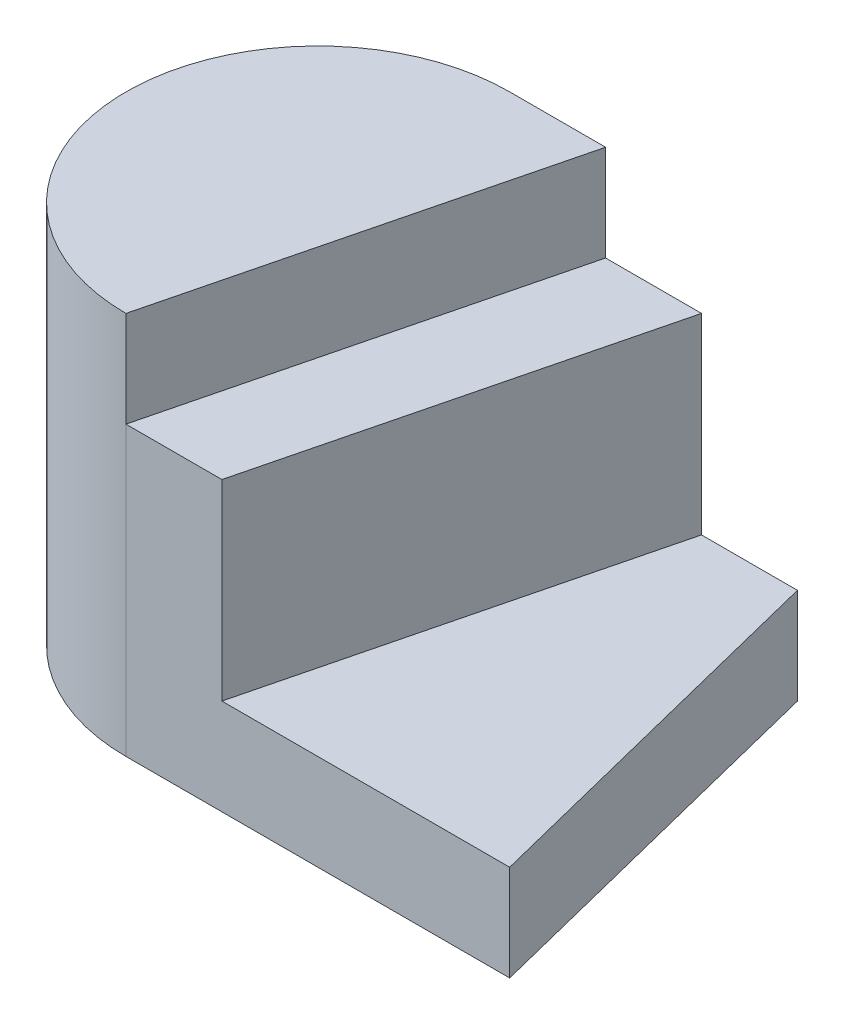
SolidWorks part; units mm, degrees
ref_plane "前基準面" through (0, 0, 0) normal (0, 0, 1) x (1, 0, 0)
ref_plane "上基準面" through (0, 0, 0) normal (0, 1, 0) x (1, 0, 0)
ref_plane "右基準面" through (0, 0, 0) normal (1, 0, 0) x (0, 0, -1)
sketch "草圖1" plane through (0, 0, 0) normal (0, 1, 0) x (1, 0, 0)
  line L0 (0, 0) -> (27.1901, 0) construction
  line L1 (0, 2) -> (3, 2)
  line L2 (3, 2) -> (4, -2)
  line L3 (4, -2) -> (0, -2)
  line L4 (0, -2) -> (1, 2)
  line L5 (1, 2) -> (2, 2)
  line L6 (2, 2) -> (1, -2)
  arc A0 (0, 2) -> (0, -2) centre (0, 0) ccw
  dimension "D1" = 4
  dimension "D2" = 3
  dimension "D3" = 4
  dimension "D4" = 1
  dimension "D5" = 1
extrude "填料-伸長2" add sketch "草圖1" along normal blind 4 contours L1 A0 L4 region at (-0.5634, 0, -0.161)
extrude "填料-伸長3" add sketch "草圖1<4>" along normal blind 3 contours L0 L4 L3 L6 | L4 L0 L6 L1 region at (1.25, 0, -1) region at (0.75, 0, 1)
sketch "草圖1<4>" plane through (0, 0, 0) normal (0, 1, 0) x (1, 0, 0) same geometry as "草圖1"
extrude "填料-伸長4" add sketch "草圖1<5>" along normal blind 1 contours L0 L6 L3 L2 | L6 L0 L2 L1 region at (2.5, 0, -0.8889) region at (2.5, 0, 1.0667)
sketch "草圖1<5>" plane through (0, 0, 0) normal (0, 1, 0) x (1, 0, 0) same geometry as "草圖1"
